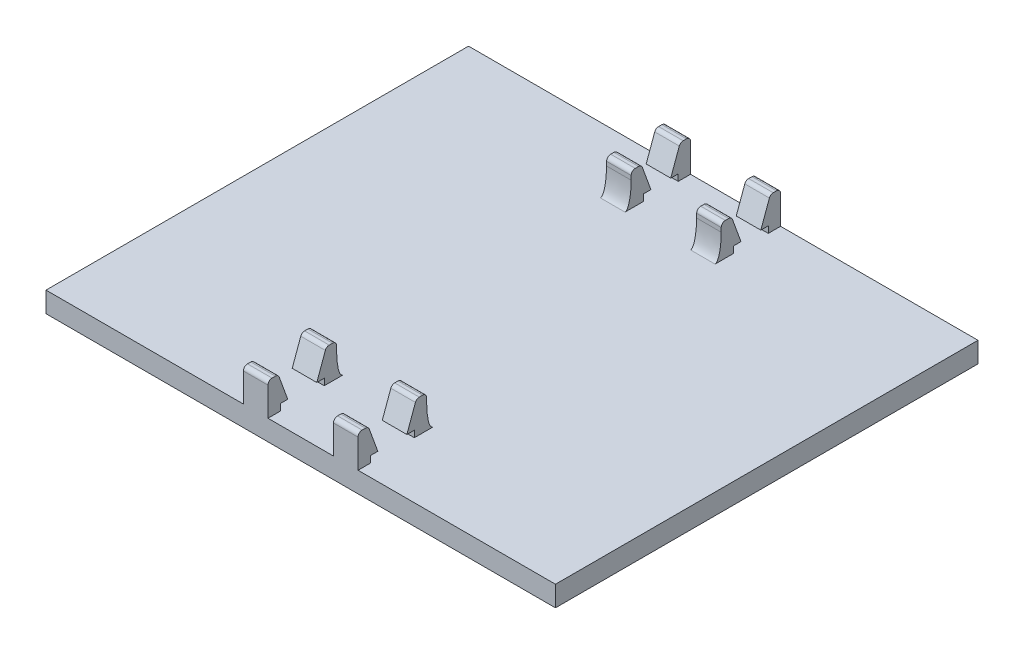
SolidWorks part; units mm, degrees
ref_plane "Front Plane" through (0, 0, 0) normal (0, 0, 1) x (1, 0, 0)
ref_plane "Top Plane" through (0, 0, 0) normal (0, 1, 0) x (1, 0, 0)
ref_plane "Right Plane" through (0, 0, 0) normal (1, 0, 0) x (0, 0, -1)
sketch "Sketch1" plane through (0, 0, 0) normal (0, 1, 0) x (1, 0, 0)
  line L1 (0, 0) -> (124.43, 0)
  line L2 (0, 0) -> (0, 103.2)
  line L3 (0, 103.2) -> (124.43, 103.2)
  line L4 (124.43, 0) -> (124.43, 103.2)
  dimension "D1" = 124.43
  dimension "D2" = 103.2
extrude "Boss-Extrude1" add sketch "Sketch1" along normal blind 5
sketch "Sketch2" plane through (0, 5, 0) normal (0, 1, 0) x (1, 0, 0)
  line L0 (124.43, 51.6) -> (0, 51.6) construction
  line L1 (124.43, 0) -> (124.43, 103.2) construction
  line L2 (0, 103.2) -> (0, 0) construction
  line L3 (62.215, 51.6) -> (62.215, 103.2) construction
  line L4 (124.43, 103.2) -> (0, 103.2) construction
  line L5 (62.215, 103.2) -> (70.215, 103.2) construction
  line L6 (48.215, 103.2) -> (48.215, 100.2)
  line L7 (70.215, 103.2) -> (76.215, 103.2)
  line L8 (70.215, 103.2) -> (70.215, 100.2)
  line L9 (70.215, 100.2) -> (76.215, 100.2)
  line L10 (76.215, 103.2) -> (76.215, 100.2)
  line L11 (54.215, 100.2) -> (48.215, 100.2)
  line L12 (54.215, 103.2) -> (54.215, 100.2)
  line L13 (54.215, 103.2) -> (48.215, 103.2)
  line L14 (54.215, 100.2) -> (54.215, 91.7) construction
  line L15 (54.215, 95.95) -> (62.215, 95.95) construction
  line L16 (76.215, 0) -> (76.215, 3)
  line L17 (70.215, 3) -> (76.215, 3)
  line L18 (70.215, 0) -> (70.215, 3)
  line L19 (70.215, 0) -> (76.215, 0)
  line L20 (54.215, 0) -> (48.215, 0)
  line L21 (54.215, 0) -> (54.215, 3)
  line L22 (54.215, 3) -> (48.215, 3)
  line L23 (48.215, 0) -> (48.215, 3)
  line L24 (54.215, 88.7) -> (48.215, 88.7)
  line L25 (54.215, 88.7) -> (54.215, 91.7)
  line L26 (54.215, 91.7) -> (48.215, 91.7)
  line L27 (48.215, 88.7) -> (48.215, 91.7)
  line L28 (76.215, 88.7) -> (76.215, 91.7)
  line L29 (70.215, 91.7) -> (76.215, 91.7)
  line L30 (70.215, 88.7) -> (70.215, 91.7)
  line L31 (70.215, 88.7) -> (76.215, 88.7)
  line L32 (54.215, 3) -> (54.215, 13.75) construction
  line L33 (54.215, 8.375) -> (62.215, 8.375) construction
  line L34 (70.215, 16.75) -> (76.215, 16.75)
  line L35 (70.215, 16.75) -> (70.215, 13.75)
  line L36 (70.215, 13.75) -> (76.215, 13.75)
  line L37 (76.215, 16.75) -> (76.215, 13.75)
  line L38 (48.215, 16.75) -> (48.215, 13.75)
  line L39 (54.215, 13.75) -> (48.215, 13.75)
  line L40 (54.215, 16.75) -> (54.215, 13.75)
  line L41 (54.215, 16.75) -> (48.215, 16.75)
  dimension "D1" = 8
  dimension "D2" = 3
  dimension "D3" = 6
  dimension "D4" = 8.5
  dimension "D5" = 10.75
extrude "Boss-Extrude2" add sketch "Sketch2" along normal blind 8
sketch "Sketch3" plane through (0, 0, -3) normal (0, 0, -1) x (-1, 0, 0)
  line L0 (-70.215, 13) -> (-70.215, 5) construction
  line L1 (-76.215, 13) -> (-70.215, 13)
  line L2 (-76.215, 13) -> (-76.215, 6.6)
  line L3 (-76.215, 6.6) -> (-70.215, 6.6)
  line L4 (-70.215, 13) -> (-70.215, 6.6)
  line L5 (-48.215, 13) -> (-48.215, 5) construction
  line L6 (-54.215, 13) -> (-48.215, 13)
  line L7 (-54.215, 13) -> (-54.215, 6.6)
  line L8 (-54.215, 6.6) -> (-48.215, 6.6)
  line L9 (-48.215, 13) -> (-48.215, 6.6)
  dimension "D1" = 6.4
extrude "Boss-Extrude3" add sketch "Sketch3" along normal blind 2
chamfer "Chamfer1" distance 2.5 angle 70 2 edges at (51.215, 13, -5) (73.215, 13, -5) first distance on face at (51.215, 13, -2.5) first distance on face at (73.215, 13, -2.5)
sketch "Sketch5" plane through (0, 0, -13.75) normal (0, 0, 1) x (1, 0, 0)
  line L0 (54.215, 13) -> (54.215, 5) construction
  line L1 (48.215, 13) -> (54.215, 13)
  line L2 (48.215, 13) -> (48.215, 6.6)
  line L3 (48.215, 6.6) -> (54.215, 6.6)
  line L4 (54.215, 13) -> (54.215, 6.6)
  line L5 (76.215, 13) -> (76.215, 5) construction
  line L6 (70.215, 13) -> (76.215, 13)
  line L7 (70.215, 13) -> (70.215, 6.6)
  line L8 (70.215, 6.6) -> (76.215, 6.6)
  line L9 (76.215, 13) -> (76.215, 6.6)
  dimension "D1" = 6.4
extrude "Boss-Extrude4" add sketch "Sketch5" along normal blind 2
chamfer "Chamfer2" distance 2.5 angle 70 2 edges at (73.215, 13, -11.75) (51.215, 13, -11.75) first distance on face at (73.215, 13, -14.25) first distance on face at (51.215, 13, -14.25)
sketch "Sketch6" plane through (0, 0, -91.7) normal (0, 0, -1) x (-1, 0, 0)
  line L0 (-70.215, 13) -> (-70.215, 5) construction
  line L1 (-76.215, 13) -> (-70.215, 13)
  line L2 (-76.215, 13) -> (-76.215, 6.6)
  line L3 (-76.215, 6.6) -> (-70.215, 6.6)
  line L4 (-70.215, 13) -> (-70.215, 6.6)
  line L5 (-48.215, 13) -> (-48.215, 5) construction
  line L6 (-54.215, 13) -> (-48.215, 13)
  line L7 (-54.215, 13) -> (-54.215, 6.6)
  line L8 (-54.215, 6.6) -> (-48.215, 6.6)
  line L9 (-48.215, 13) -> (-48.215, 6.6)
  dimension "D1" = 6.4
extrude "Boss-Extrude5" add sketch "Sketch6" along normal blind 2
chamfer "Chamfer3" distance 2.5 angle 70 2 edges at (51.215, 13, -93.7) (73.215, 13, -93.7) first distance on face at (51.215, 13, -91.2) first distance on face at (73.215, 13, -91.2)
sketch "Sketch7" plane through (0, 0, -100.2) normal (0, 0, 1) x (1, 0, 0)
  line L0 (54.215, 13) -> (54.215, 5) construction
  line L1 (48.215, 13) -> (54.215, 13)
  line L2 (48.215, 13) -> (48.215, 6.6)
  line L3 (48.215, 6.6) -> (54.215, 6.6)
  line L4 (54.215, 13) -> (54.215, 6.6)
  line L5 (76.215, 13) -> (76.215, 5) construction
  line L6 (70.215, 13) -> (76.215, 13)
  line L7 (70.215, 13) -> (70.215, 6.6)
  line L8 (70.215, 6.6) -> (76.215, 6.6)
  line L9 (76.215, 13) -> (76.215, 6.6)
  dimension "D1" = 6.4
extrude "Boss-Extrude6" add sketch "Sketch7" along normal blind 2
chamfer "Chamfer4" distance 2.5 angle 70 2 edges at (73.215, 13, -98.2) (51.215, 13, -98.2) first distance on face at (73.215, 13, -100.7) first distance on face at (51.215, 13, -100.7)
fillet "Fillet1" radius 1 16 edges at (51.215, 13, -2.5) (73.215, 13, -2.5) (73.215, 13, 0) (51.215, 13, 0) (51.215, 13, -14.25) (51.215, 13, -16.75) (73.215, 13, -16.75) (73.215, 13, -14.25) (73.215, 13, -100.7) (73.215, 13, -91.2) (73.215, 13, -88.7) (73.215, 13, -103.2) (51.215, 13, -103.2) (51.215, 13, -100.7) (51.215, 13, -91.2) (51.215, 13, -88.7)
fillet "Fillet2" radius 1.5 4 edges at (51.215, 5, -88.7) (73.215, 5, -88.7) (51.215, 5, -16.75) (73.215, 5, -16.75) second distance 6 first distance on face at (51.215, 5, -15.25)
sketch "Sketch8" plane through (0, 5, 0) normal (0, 1, 0) x (1, 0, 0)
  line L0 (124.43, 103.2) -> (124.43, 81.6) construction
  line L1 (124.43, 0) -> (124.43, 103.2) construction
  line L2 (124.43, 81.6) -> (124.43, 21.6) construction
  line L3 (124.43, 21.6) -> (124.43, 0) construction
  dimension "D1" = 60
equation "\"leftedgewidth\" = 8.5mm"
equation "\"rightedgewidth\" = 10.75mm"
equation "\"innerclipwidth\" = 11.5mm"
equation "\"innerframewidth\" = 99.18mm"
equation "\"framelength\" = 103.2mm"
equation "\"D2@Sketch1\"=\"framelength\""
equation "\"basethickness\" = 5mm"
equation "\"D1@Boss-Extrude1\"=\"basethickness\""
equation "\"clipwidth\" = 3mm"
equation "\"cliplength\" = 6mm"
equation "\"clipheight\" = 8mm"
equation "\"framethickness\" = 1.6mm"
equation "\"D1@Sketch3\"=\"clipheight\"-\"framethickness\""
